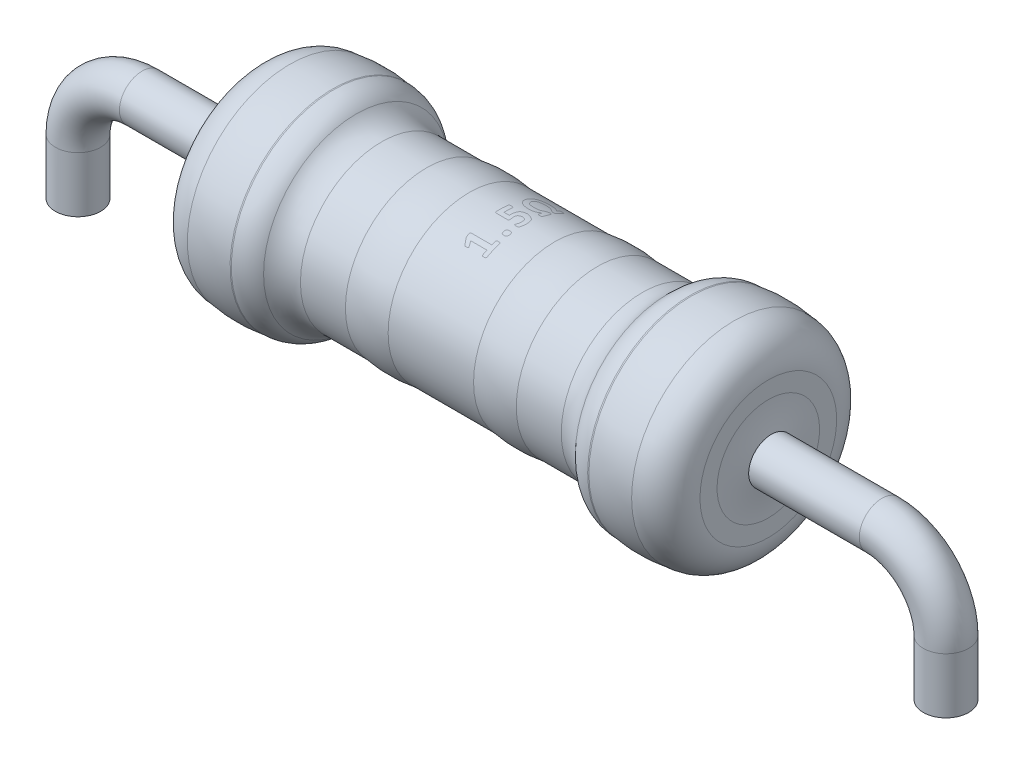
SolidWorks part; units mm, degrees
material "Plain Carbon Steel"
ref_plane "Front Plane" through (0, 0, 0) normal (0, 0, 1) x (1, 0, 0)
ref_plane "Top Plane" through (0, 0, 0) normal (0, 1, 0) x (1, 0, 0)
ref_plane "Right Plane" through (0, 0, 0) normal (1, 0, 0) x (0, 0, -1)
sketch "Sketch1" plane through (0, 0, 0) normal (0, 0, 1) x (1, 0, 0)
  line L0 (-4.33, 0) -> (4.33, 0)
  line L1 (-5.08, -0.75) -> (-5.08, -25.4)
  line L2 (5.08, -0.75) -> (5.08, -25.4)
  line L3 (-5.08, -25.4) -> (5.08, -25.4) construction
  line L4 (0, 0) -> (0, -25.4) construction
  arc A0 (-4.33, 0) -> (-5.08, -0.75) centre (-4.33, -0.75) ccw
  arc A1 (4.33, 0) -> (5.08, -0.75) centre (4.33, -0.75) cw
  dimension "D2" = 0.75
  dimension "D1" = 10.16
  dimension "D3" = 25.4
ref_plane "Plane1" through (-5.08, -25.4, 0) normal (0, -1, 0) x (-1, 0, 0)
sketch "Sketch2" plane through (-5.08, -25.4, 0) normal (0, -1, 0) x (-1, 0, 0)
  circle A0 centre (0, 0) radius 0.265
  dimension "D1" = 0.53
sweep "Sweep1" add profiles "Sketch2" path "Sketch1"
sketch "Sketch3" plane through (0, 0, 0) normal (0, 0, 1) x (1, 0, 0)
  line L0 (-3, 0) -> (3, 0)
  line L5 (-3, 0) -> (-3, 1.2)
  line L6 (3, 0) -> (3, 1.2)
  line L7 (-3, 1.2) -> (-1.75, 1.2)
  line L8 (3, 1.2) -> (1.75, 1.2)
  line L9 (-1.75, 1.2) -> (-1.75, 0.95)
  line L10 (-1.75, 0.95) -> (1.75, 0.95)
  line L11 (1.75, 0.95) -> (1.75, 1.2)
  line L12 (0, 0) -> (0, 0.95) construction
  dimension "D1" = 6
  dimension "D2" = 1.2
  dimension "D3" = 3.5
  dimension "D4" = 0.95
  dimension "D5" = 0.25
revolve "Revolve1" add sketch "Sketch3" angle 360 about L0
fillet "Fillet-1" radius 0.35 2 edges at (1.75, 0, 1.2) (-1.75, 0, 1.2)
fillet "Fillet-2" radius 0.4 4 edges at (3, 0, 1.2) (-3, 0, 1.2) (1.75, 0, 0.95) (-1.75, 0, 0.95)
sketch "Sketch5" plane through (0, 0, 0) normal (0, 0, 1) x (1, 0, 0)
  line L16 (-3, 0) -> (3, 0) construction
  line L17 (-2.6, 1.2) -> (-2.1, 1.2) construction
  line L18 (-2.6, 1.2) -> (-2.6, 0)
  line L19 (-2.6, 0) -> (-2.1, 0)
  line L20 (-2.1, 1.2) -> (-2.1, 0)
  line L21 (-1.75, 0.95) -> (1.75, 0.95) construction
  line L22 (2.6, 1.2) -> (2.1, 1.2) construction
  line L23 (2.6, 1.2) -> (2.6, 0)
  line L24 (2.6, 0) -> (2.1, 0)
  line L25 (2.1, 1.2) -> (2.1, 0)
  line L26 (-0.5, 0.95) -> (-1, 0.95) construction
  line L27 (-0.5, 0.95) -> (-0.5, 0)
  line L28 (-0.5, 0) -> (-1, 0)
  line L29 (-1, 0.95) -> (-1, 0)
  line L30 (-2.35, 1.2) -> (-2.35, 1.22) construction
  line L31 (1, 0.95) -> (0.5, 0.95) construction
  line L32 (1, 0.95) -> (1, 0)
  line L33 (1, 0) -> (0.5, 0)
  line L34 (0.5, 0.95) -> (0.5, 0)
  line L35 (-0.75, 0.95) -> (-0.75, 0.97) construction
  line L36 (0.75, 0.95) -> (0.75, 0.97) construction
  line L37 (2.35, 1.2) -> (2.35, 1.22) construction
  line L48 (-3, 0) -> (-3, 0.6)
  line L49 (-3, 0) -> (-3, 1.2) construction
  line L50 (-3, 0) -> (-3.05, 0)
  line L51 (-3.05, 0) -> (-3.05, 0.2)
  line L52 (3, 0) -> (3.05, 0)
  line L53 (3.05, 0) -> (3.05, 0.2)
  line L54 (3, 0) -> (3, 0.6)
  line L55 (3, 0) -> (3, 1.2) construction
  arc A0 (-2.6, 1.2) -> (-2.1, 1.2) centre (-2.35, -0.3525) cw
  arc A1 (-1, 0.95) -> (-0.5, 0.95) centre (-0.75, -0.6025) cw
  arc A2 (0.5, 0.95) -> (1, 0.95) centre (0.75, -0.6025) cw
  arc A3 (2.1, 1.2) -> (2.6, 1.2) centre (2.35, -0.3525) cw
  arc A6 (-3, 0.6) -> (-3.05, 0.2) centre (-4.625, 0.6) cw
  arc A7 (3.05, 0.2) -> (3, 0.6) centre (4.625, 0.6) cw
  dimension "D4" = 0.02
  dimension "D5" = 0.05
  dimension "D7" = 0.6
  dimension "D1" = 0.5
  dimension "D2" = 0.5
  dimension "D3" = 0.5
  dimension "D6" = 0.2
revolve "Revolve3" add sketch "Sketch5" angle 360 about L19
ref_plane "Plane2" through (0, 2, 0) normal (0, 1, 0) x (1, 0, 0)
sketch "Sketch6" plane through (0, 2, 0) normal (0, 1, 0) x (1, 0, 0)
  line L0 (0, 0) -> (0.15, 0) construction
  line L1 (0.15, 0.95) -> (0.15, -0.95) construction
  line L2 (0.5, 0.95) -> (-0.5, 0.95) construction
  text T0 "1.5Ω" font "Calibri" height 0.3
  dimension "D1" = 0.15
wrap "Wrap1" sketch "Sketch6" wrap type scribe source sketch "Sketch6" face at (-0.5, -0.95, 0)
sketch "Skizze1" plane through (0, -25.4, 0) normal (0, -1, 0) x (1, 0, 0)
  line L1 (7.6543, -1.9603) -> (-7.2437, -1.9603)
  line L2 (7.6543, -1.9603) -> (7.6543, 2.6249)
  line L3 (7.6543, 2.6249) -> (-7.2437, 2.6249)
  line L4 (-7.2437, -1.9603) -> (-7.2437, 2.6249)
extrude "Schnitt-Linear austragen1" cut sketch "Skizze1" against normal blind 24
